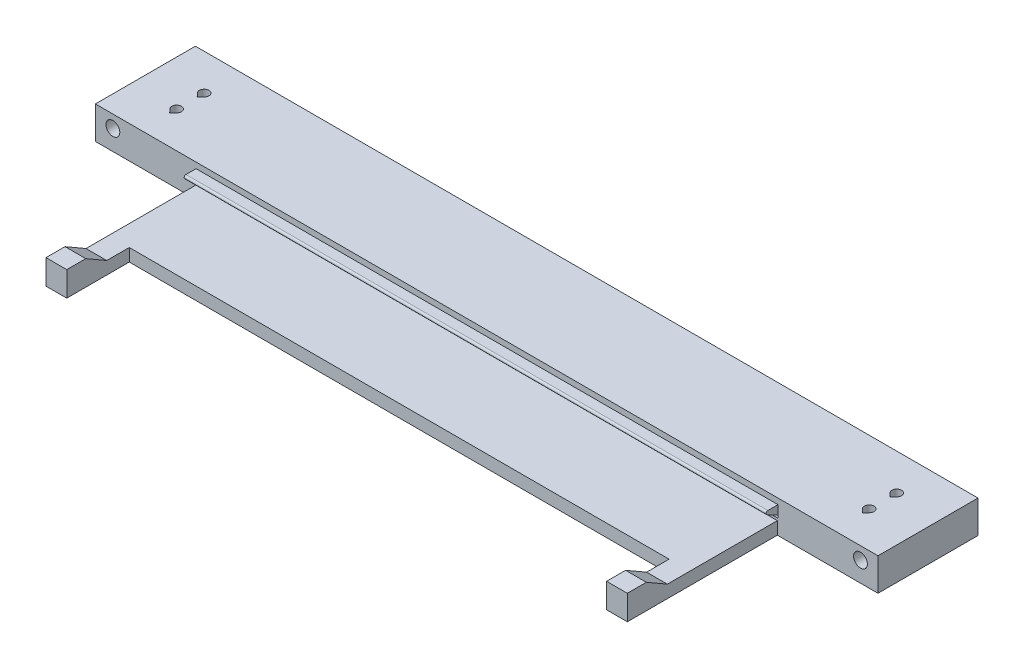
SolidWorks part; units mm, degrees
ref_plane "Front Plane" through (0, 0, 0) normal (0, 0, 1) x (1, 0, 0)
ref_plane "Top Plane" through (0, 0, 0) normal (0, 1, 0) x (1, 0, 0)
ref_plane "Right Plane" through (0, 0, 0) normal (1, 0, 0) x (0, 0, -1)
sketch "Sketch1" plane through (0, 0, 0) normal (1, 0, 0) x (0, 0, -1)
  line L1 (0, 0) -> (40, 0)
  line L2 (0, 0) -> (0, 10)
  line L3 (0, 10) -> (40, 10)
  line L4 (40, 0) -> (40, 10)
  dimension "D1" = 10
  dimension "D2" = 40
extrude "Boss-Extrude1" add sketch "Sketch1" along normal blind 312.998
sketch "Sketch2" plane through (0, 0, -40) normal (0, 0, -1) x (-1, 0, 0)
  line L1 (-272.994, 3) -> (-40.004, 3)
  line L2 (-272.994, 3) -> (-272.994, 4.2)
  line L3 (-272.994, 4.2) -> (-40.004, 4.2)
  line L4 (-40.004, 3) -> (-40.004, 4.2)
  line L5 (-272.994, 4.2) -> (-312.998, 0) construction
  line L6 (-40.004, 4.2) -> (0, 0) construction
  line L7 (-312.998, 0) -> (0, 0) construction
  dimension "D1" = 232.99
  dimension "D2" = 3
  dimension "D3" = 1.2
extrude "Cut-Extrude1" cut sketch "Sketch2" against normal through all
sketch "Sketch3" plane through (0, 10, 0) normal (0, 1, 0) x (1, 0, 0)
  line L0 (156.499, 71.4665) -> (156.499, -49.9307) construction
  line L1 (0, 40) -> (156.499, 71.4665) construction
  line L2 (156.499, 71.4665) -> (312.998, 40) construction
  line L3 (312.998, 40) -> (312.998, 0) construction
  line L4 (312.998, 40) -> (0, 40) construction
  line L5 (312.998, 40) -> (294.998, 25.5) construction
  line L6 (294.998, 25.5) -> (294.998, 14.5) construction
  line L7 (294.998, 14.5) -> (312.998, 0) construction
  circle A0 centre (294.998, 25.5) radius 1.9177
  circle A1 centre (294.998, 14.5) radius 1.9177
  circle A2 centre (18, 14.5) radius 1.9177
  circle A3 centre (18, 25.5) radius 1.9177
  dimension "D3" = 3.8354
  dimension "D1" = 18
  dimension "D2" = 14.5
extrude "Cut-Extrude2" cut sketch "Sketch3" against normal through all
sketch "Sketch4" plane through (0, 0, 0) normal (0, -1, 0) x (1, 0, 0)
  line L1 (14.5837, -12.5276) -> (14.5837, -16.4724)
  line L2 (14.5837, -16.4724) -> (18, -18.4448)
  line L3 (18, -18.4448) -> (21.4163, -16.4724)
  line L4 (21.4163, -16.4724) -> (21.4163, -12.5276)
  line L5 (21.4163, -12.5276) -> (18, -10.5552)
  line L6 (18, -10.5552) -> (14.5837, -12.5276)
  line L7 (14.5837, -23.5276) -> (14.5837, -27.4724)
  line L8 (14.5837, -27.4724) -> (18, -29.4448)
  line L9 (18, -29.4448) -> (21.4163, -27.4724)
  line L10 (21.4163, -27.4724) -> (21.4163, -23.5276)
  line L11 (21.4163, -23.5276) -> (18, -21.5552)
  line L12 (18, -21.5552) -> (14.5837, -23.5276)
  line L13 (298.4143, -12.5276) -> (294.998, -10.5552)
  line L14 (294.998, -10.5552) -> (291.5817, -12.5276)
  line L15 (291.5817, -12.5276) -> (291.5817, -16.4724)
  line L16 (291.5817, -16.4724) -> (294.998, -18.4448)
  line L17 (294.998, -18.4448) -> (298.4143, -16.4724)
  line L18 (298.4143, -16.4724) -> (298.4143, -12.5276)
  line L19 (291.5817, -23.5276) -> (291.5817, -27.4724)
  line L20 (291.5817, -27.4724) -> (294.998, -29.4448)
  line L21 (294.998, -29.4448) -> (298.4143, -27.4724)
  line L22 (298.4143, -27.4724) -> (298.4143, -23.5276)
  line L23 (298.4143, -23.5276) -> (294.998, -21.5552)
  line L24 (294.998, -21.5552) -> (291.5817, -23.5276)
  circle A0 centre (18, -14.5) radius 3.4163 construction
  circle A1 centre (18, -25.5) radius 3.4163 construction
  circle A2 centre (294.998, -14.5) radius 3.4163 construction
  circle A3 centre (294.998, -25.5) radius 3.4163 construction
  dimension "D1" = 6.8326
extrude "Cut-Extrude3" cut sketch "Sketch4" against normal blind 4.3
sketch "Sketch5" plane through (0, 0, 0) normal (0, 0, 1) x (1, 0, 0)
  line L0 (0, 10) -> (7, 5) construction
  line L1 (7, 5) -> (0, 0) construction
  line L2 (0, 10) -> (156.499, 87.0064) construction
  line L3 (156.499, 87.0064) -> (312.998, 10) construction
  line L4 (312.998, 10) -> (312.998, 0) construction
  line L5 (312.998, 10) -> (0, 10) construction
  line L6 (156.499, 87.0064) -> (156.499, -80.9825) construction
  line L7 (305.998, 5) -> (312.998, 0) construction
  line L8 (312.998, 10) -> (305.998, 5) construction
  circle A0 centre (7, 5) radius 2.7623
  circle A1 centre (305.998, 5) radius 2.7623
  dimension "D1" = 5.5245
  dimension "D2" = 7
extrude "Cut-Extrude4" cut sketch "Sketch5" against normal through all
sketch "Sketch6" plane through (0, 0, 0) normal (-1, 0, 0) x (0, 0, 1)
  line L0 (-40, 10) -> (-33, 8.4163) construction
  line L1 (-33, 8.4163) -> (-29, 8.4163)
  line L2 (-33, 8.4163) -> (-33, 1.5837)
  line L3 (-33, 1.5837) -> (-29, 1.5837)
  line L4 (-29, 8.4163) -> (-29, 1.5837)
  line L9 (-33, 1.5837) -> (-40, 0) construction
  line L10 (-40, 10) -> (-20, 18.9404) construction
  line L11 (-20, 18.9404) -> (0, 10) construction
  line L12 (-20, 18.9404) -> (-20, -7.3414) construction
  line L13 (-7, 1.5837) -> (0, 0) construction
  line L14 (0, 10) -> (-7, 8.4163) construction
  line L15 (-11, 8.4163) -> (-11, 1.5837)
  line L16 (-7, 1.5837) -> (-11, 1.5837)
  line L17 (-7, 8.4163) -> (-7, 1.5837)
  line L18 (-7, 8.4163) -> (-11, 8.4163)
  dimension "D1" = 7
  dimension "D2" = 4
  dimension "D3" = 6.8326
extrude "Cut-Extrude5" cut sketch "Sketch6" against normal blind 15
ref_plane "Plane1" through (156.499, 0, 0) normal (-1, 0, 0) x (0, 0, 1)
sketch "Sketch7" plane through (0, 0, 0) normal (0, 0, 1) x (1, 0, 0)
  line L0 (312.998, 0) -> (0, 0) construction
  line L1 (40.249, 0) -> (272.749, 0)
  line L2 (40.249, 0) -> (40.249, 2.0463)
  line L3 (40.249, 2.0463) -> (272.749, 2.0463)
  line L4 (272.749, 0) -> (272.749, 2.0463)
  line L5 (40.249, 2.0463) -> (40.004, 4.2) construction
  line L6 (272.994, 4.2) -> (272.749, 2.0463) construction
  dimension "D1" = 232.5
extrude "Boss-Extrude2" add sketch "Sketch7" along normal blind 60
sketch "Sketch8" plane through (0, 2.0463, 0) normal (0, 1, 0) x (1, 0, 0)
  line L0 (272.749, -60) -> (40.249, -60) construction
  line L1 (48.549, -35) -> (264.449, -35)
  line L2 (48.549, -35) -> (48.549, -60)
  line L3 (48.549, -60) -> (264.449, -60)
  line L4 (264.449, -35) -> (264.449, -60)
  line L5 (48.549, -35) -> (40.249, -60) construction
  line L6 (272.749, -60) -> (264.449, -35) construction
  dimension "D1" = 25
  dimension "D2" = 215.9
extrude "Cut-Extrude6" cut sketch "Sketch8" against normal up to next
sketch "Sketch9" plane through (0, 0, 0) normal (0, -1, 0) x (1, 0, 0)
  line L0 (0, -40) -> (0, 0)
  line L1 (0, 0) -> (40.249, 0)
  line L2 (40.249, 0) -> (40.249, 60)
  line L3 (40.249, 60) -> (48.549, 60)
  line L4 (48.549, 60) -> (48.549, 35)
  line L5 (48.549, 35) -> (264.449, 35)
  line L6 (264.449, 35) -> (264.449, 60)
  line L7 (264.449, 60) -> (272.749, 60)
  line L8 (272.749, 60) -> (272.749, 0)
  line L9 (272.749, 0) -> (312.998, 0)
  line L10 (312.998, 0) -> (312.998, -40)
  line L11 (312.998, -40) -> (0, -40)
  line L12 (21.4163, -16.4724) -> (21.4163, -12.5276) construction
  line L13 (17.9977, -10.5552) -> (14.5825, -12.5296)
  line L14 (14.5825, -12.5296) -> (14.5849, -16.4744)
  line L15 (14.5849, -16.4744) -> (18.0023, -18.4448)
  line L16 (18.0023, -18.4448) -> (21.4175, -16.4704)
  line L17 (21.4175, -16.4704) -> (21.4151, -12.5256)
  line L18 (21.4151, -12.5256) -> (17.9977, -10.5552)
  line L19 (18.0023, -21.5552) -> (14.5849, -23.5256)
  line L20 (14.5849, -23.5256) -> (14.5825, -27.4704)
  line L21 (14.5825, -27.4704) -> (17.9977, -29.4448)
  line L22 (17.9977, -29.4448) -> (21.4151, -27.4744)
  line L23 (21.4151, -27.4744) -> (21.4175, -23.5296)
  line L24 (21.4175, -23.5296) -> (18.0023, -21.5552)
  line L25 (295.0003, -10.5552) -> (291.5828, -12.5256)
  line L26 (291.5828, -12.5256) -> (291.5805, -16.4704)
  line L27 (291.5805, -16.4704) -> (294.9956, -18.4448)
  line L28 (294.9956, -18.4448) -> (298.4131, -16.4744)
  line L29 (298.4131, -16.4744) -> (298.4154, -12.5296)
  line L30 (298.4154, -12.5296) -> (295.0003, -10.5552)
  line L31 (294.9956, -21.5552) -> (291.5805, -23.5296)
  line L32 (291.5805, -23.5296) -> (291.5828, -27.4744)
  line L33 (291.5828, -27.4744) -> (295.0003, -29.4448)
  line L34 (295.0003, -29.4448) -> (298.4154, -27.4704)
  line L35 (298.4154, -27.4704) -> (298.4131, -23.5256)
  line L36 (298.4131, -23.5256) -> (294.9956, -21.5552)
  circle A0 centre (18, -14.5) radius 3.4163 construction
  circle A1 centre (18, -25.5) radius 3.4163 construction
  circle A2 centre (294.998, -14.5) radius 3.4163 construction
  circle A3 centre (294.998, -25.5) radius 3.4163 construction
extrude "Boss-Extrude3" add sketch "Sketch9" along normal blind 3
sketch "Sketch10" plane through (40.249, 0, 0) normal (-1, 0, 0) x (0, 0, 1)
  line L1 (60, 2.0463) -> (42, 2.0463)
  line L2 (60, 2.0463) -> (60, 6.8906)
  line L3 (60, 6.8906) -> (42, 6.8906)
  line L4 (42, 2.0463) -> (42, 6.8906)
  dimension "D1" = 18
extrude "Boss-Extrude4" add sketch "Sketch10" against normal up to surface (8.3 mm away) up to face at (48.549, -0.4768, 47.5)
sketch "Sketch12" plane through (40.249, 0, 0) normal (-1, 0, 0) x (0, 0, 1)
  line L4 (0, 4.2) -> (7, 7.7)
  line L5 (7, 7.7) -> (0, 7.7)
  line L6 (0, 7.7) -> (0, 4.2)
  line L7 (0, 10) -> (0, -3) construction
  dimension "D1" = 7
  dimension "D2" = 3.5
extrude "Boss-Extrude6" add sketch "Sketch12" against normal up to surface (232.745 mm away) up to face at (272.994, 3.6, -20)
fillet "Fillet1" radius 0.7 1 edges at (156.6215, 7.7, 7)
sketch "Sketch15" plane through (0, 2.0463, 0) normal (0, 1, 0) x (1, 0, 0)
  line L1 (264.449, -42) -> (272.749, -42)
  line L2 (264.449, -42) -> (264.449, -60)
  line L3 (264.449, -60) -> (272.749, -60)
  line L4 (272.749, -42) -> (272.749, -60)
  dimension "D1" = 18
extrude "Boss-Extrude8" add sketch "Sketch15" along normal up to surface (4.8443 mm away) up to face at (44.399, 6.8906, 51)
sketch "Sketch16" plane through (0, 10, 0) normal (0, 1, 0) x (1, 0, 0)
  line L0 (0, 40) -> (156.499, 106.783) construction
  line L1 (156.499, 106.783) -> (312.998, 40) construction
  line L2 (156.499, 106.783) -> (156.499, -99.1914) construction
  line L3 (18, 25.5009) -> (18, 14.5009) construction
  line L4 (16.6158, 24.1728) -> (18, 22.7292)
  line L5 (19.3842, 24.1728) -> (18, 22.7292)
  line L6 (16.6158, 13.1728) -> (18, 11.7292)
  line L7 (19.3842, 13.1728) -> (18, 11.7292)
  line L8 (293.6138, 13.1728) -> (294.998, 11.7292)
  line L9 (296.3822, 13.1728) -> (294.998, 11.7292)
  line L10 (293.6138, 24.1728) -> (294.998, 22.7292)
  line L11 (296.3822, 24.1728) -> (294.998, 22.7292)
  circle A0 centre (18, 25.5) radius 1.9177 construction
  arc A1 (16.6158, 24.1728) -> (19.3842, 24.1728) centre (18, 25.5) ccw
  arc A2 (16.6158, 13.1728) -> (19.3842, 13.1728) centre (18, 14.5) ccw
  arc A3 (296.3822, 13.1728) -> (293.6138, 13.1728) centre (294.998, 14.5) cw
  arc A4 (296.3822, 24.1728) -> (293.6138, 24.1728) centre (294.998, 25.5) cw
  point P27 (0, 0)
  point P28 (18, 22.9554)
  dimension "D2" = 2
  dimension "D1" = 2
extrude "Cut-Extrude8" cut sketch "Sketch16" against normal through all
chamfer "Chamfer1" distance 6 angle 60 2 edges at (44.399, 6.8906, 42) (268.599, 6.8906, 42) first distance on face at (44.399, 4.4685, 42) first distance on face at (268.599, 4.4685, 42)
